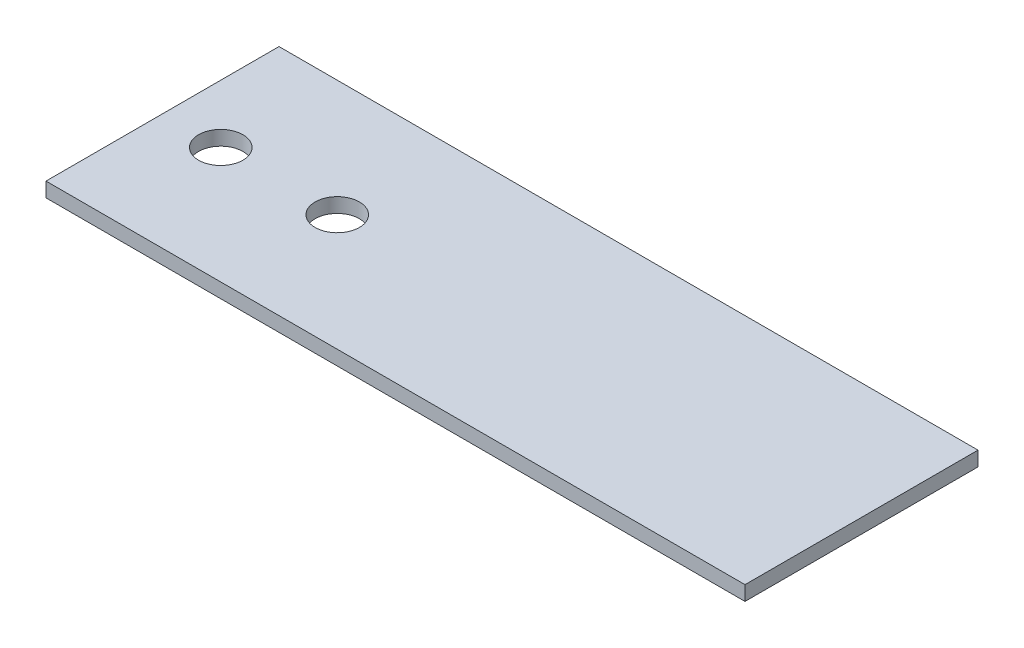
SolidWorks part; units mm, degrees
material "201 Annealed Stainless Steel (SS)"
ref_plane "Front Plane" through (0, 0, 0) normal (0, 0, 1) x (1, 0, 0)
ref_plane "Top Plane" through (0, 0, 0) normal (0, 1, 0) x (1, 0, 0)
ref_plane "Right Plane" through (0, 0, 0) normal (1, 0, 0) x (0, 0, -1)
sketch "Sketch1" plane through (0, 0, 0) normal (0, 1, 0) x (1, 0, 0)
  line L1 (0, 0) -> (76.2, 0)
  line L2 (0, 0) -> (0, 25.4)
  line L3 (0, 25.4) -> (76.2, 25.4)
  line L4 (76.2, 0) -> (76.2, 25.4)
  dimension "D1" = 76.2
  dimension "D2" = 25.4
extrude "Electrode Base" add sketch "Sketch1" along normal blind 1.5875
sketch "Sketch2" plane through (0, 1.5875, 0) normal (0, 1, 0) x (1, 0, 0)
  line L0 (0, 12.7) -> (76.2, 12.7) construction
  line L1 (0, 25.4) -> (0, 0) construction
  line L2 (76.2, 0) -> (76.2, 25.4) construction
  line L3 (38.1, 25.4) -> (38.1, 0) construction
  line L4 (76.2, 25.4) -> (0, 25.4) construction
  line L5 (0, 0) -> (76.2, 0) construction
  circle A0 centre (6.35, 12.7) radius 2.413
  circle A1 centre (19.05, 12.7) radius 2.413
  dimension "D1" = 4.826
  dimension "D2" = 4.826
  dimension "D4" = 12.7
  dimension "D3" = 6.35
extrude "Cut-Extrude1" cut sketch "Sketch2" against normal through all
